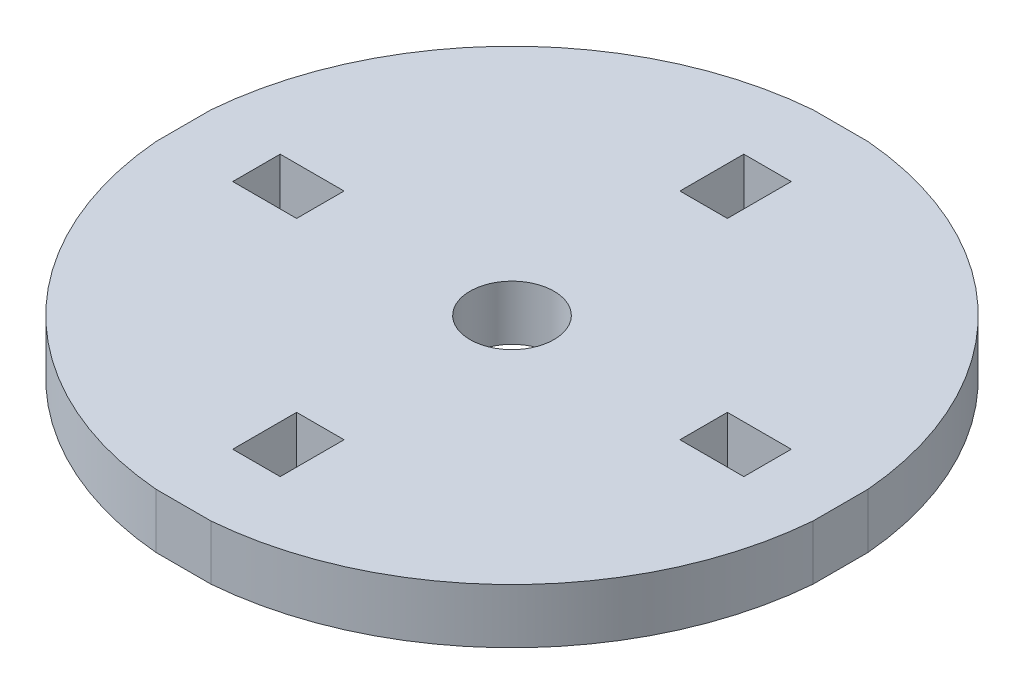
SolidWorks part; units mm, degrees
ref_plane "Front Plane" through (0, 0, 0) normal (0, 0, 1) x (1, 0, 0)
ref_plane "Top Plane" through (0, 0, 0) normal (0, 1, 0) x (1, 0, 0)
ref_plane "Right Plane" through (0, 0, 0) normal (1, 0, 0) x (0, 0, -1)
sketch "Sketch1" plane through (0, 0, 0) normal (0, 1, 0) x (1, 0, 0)
  line L0 (-1.5, -18) -> (1.5, -18)
  line L1 (0, -95) -> (0, 0) construction
  line L3 (0, -14) -> (0, -10.5) construction
  line L5 (1.3, -14) -> (-1.3, -14)
  line L6 (1.3, -14) -> (1.3, -10.5)
  line L7 (1.3, -10.5) -> (-1.3, -10.5)
  line L8 (-1.3, -14) -> (-1.3, -10.5)
  line L9 (0, -10.5) -> (0, -14) construction
  line L10 (1.3, -12.25) -> (-1.3, -12.25) construction
  line L13 (-18, 1.5) -> (-18, -1.5)
  line L14 (1.5, 18) -> (-1.5, 18)
  line L15 (18, -1.5) -> (18, 1.5)
  line L16 (-10.5, -1.3) -> (-10.5, 1.3)
  line L17 (-14, 1.3) -> (-10.5, 1.3)
  line L18 (-14, -1.3) -> (-14, 1.3)
  line L19 (-14, -1.3) -> (-10.5, -1.3)
  line L20 (-1.3, 10.5) -> (1.3, 10.5)
  line L21 (1.3, 14) -> (1.3, 10.5)
  line L22 (-1.3, 14) -> (1.3, 14)
  line L23 (-1.3, 14) -> (-1.3, 10.5)
  line L24 (10.5, 1.3) -> (10.5, -1.3)
  line L25 (14, -1.3) -> (10.5, -1.3)
  line L26 (14, 1.3) -> (14, -1.3)
  line L27 (14, 1.3) -> (10.5, 1.3)
  circle A0 centre (0, 0) radius 2.3
  arc A2 (-18, -1.5) -> (-1.5, -18) centre (0, 0) ccw
  arc A3 (-18, 1.5) -> (-1.5, 18) centre (0, 0) cw
  arc A4 (1.5, 18) -> (18, 1.5) centre (0, 0) cw
  arc A5 (18, -1.5) -> (1.5, -18) centre (0, 0) cw
  point P5 (0, -18)
  point P6 (0, -12.25)
  point P9 (0, 0)
  point P10 (0, -17.97)
  point P11 (0, -12.25)
  point P17 (0, -17.8111)
  point P18 (0, 0)
  point P19 (0, 0)
  point P32 (0, 0)
  point P49 (0, 0)
  dimension "D1" = 4.6
  dimension "D3" = 2.6
  dimension "D4" = 3
  dimension "D5" = 4
  dimension "D6" = 4
extrude "Boss-Extrude1" add sketch "Sketch1" along normal blind 3
